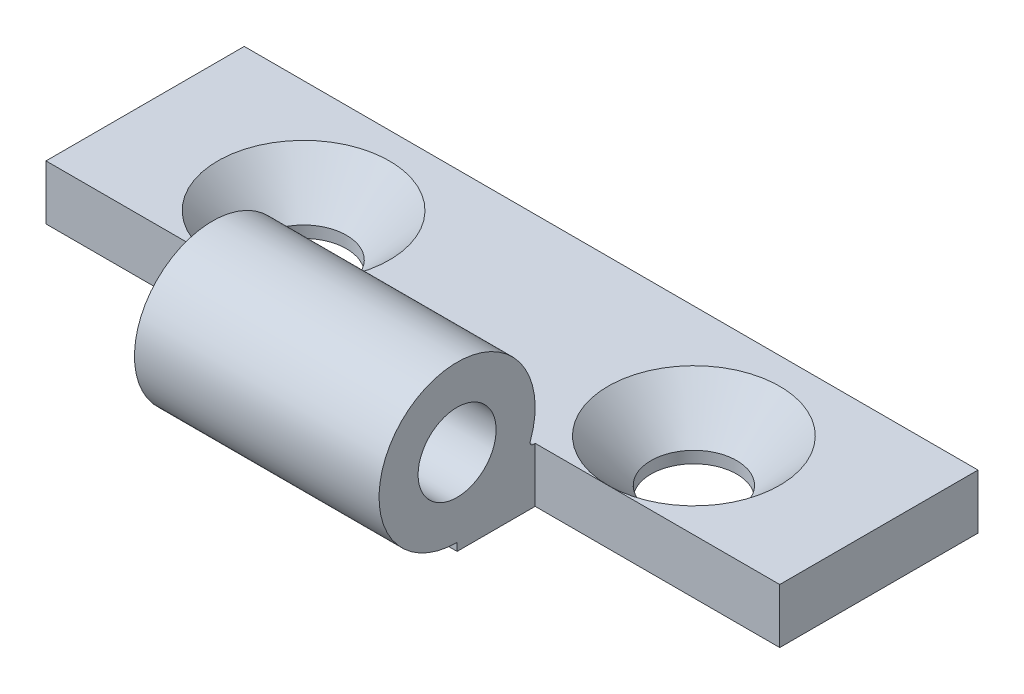
SolidWorks part; units mm, degrees
note: '?' marks a value the reader was unsure of.
ref_plane "Front Plane" through (0, 0, 0) normal (0, 0, 1) x (1, 0, 0)
ref_plane "Top Plane" through (0, 0, 0) normal (0, 1, 0) x (1, 0, 0)
ref_plane "Right Plane" through (0, 0, 0) normal (1, 0, 0) x (0, 0, -1)
ref_axis "Axis_X" through (-13.35, 0, 0) along (1, 0, 0)?
ref_axis "Axis_Y" through (0, 11.025, 0) along (0, -1, 0)?
ref_axis "Axis_Z" through (0, 0, -8.335) along (0, 0, 1)?
ref_plane "K" through (-11, 0, 0) normal (1, 0, 0) x (0, 0, -1)
ref_plane "L" through (36, 0, 0) normal (1, 0, 0) x (0, 0, -1)
sketch "Sketch1" plane through (0, 0, 0) normal (1, 0, 0) x (0, 0, -1)
  line L9 (-10.5, 0.5) -> (-10.5, 0)
  line L10 (7.2, 0) -> (7.2, 3.5)
  line L11 (7.2, 3.5) -> (-5.6215, 3.5)
  line L12 (7.2, 0) -> (-10.5, 0)
  circle A0 centre (-10.5, 5.5) radius 2.5
  arc A3 (-5.8091, 3.7692) -> (-10.5, 0.5) centre (-10.5, 5.5) ccw
  arc A4 (-5.8091, 3.7692) -> (-5.6215, 3.5) centre (-5.6215, 3.7) ccw
  dimension "R" = 5
  dimension "FIX_1" = 5
  dimension "FIX_2" = 0.2
  dimension "T" = 3.5
  dimension "MSM_2" = 17.7
  dimension "E" = 5.5
  dimension "J" = 7.2
extrude "Boss-Extrude1" add sketch "Sketch1" along normal up to surface (36 mm away) and the other way up to surface (11 mm away) up to plane "L" other way up to plane "K"
hole_wizard "CSK1" positions "Sketch3" profile "Sketch2" countersink size "M5" standard "JIS" end condition through all
sketch "Sketch3" plane through (0, 3.5, 0) normal (0, 1, 0) x (1, 0, 0)
  point P0 (0, 0)
  point P3 (25, 0)
  dimension "P" = 25
sketch "Sketch2" plane through (0, 3.5, 0) normal (1, 0, 0) x (0, 0, 1)
  line L0 (0, 0) -> (0, 3.5)
  line L1 (0, 3.5) -> (2.75, 3.5)
  line L2 (2.75, 3.5) -> (2.75, 2.75)
  line L3 (2.75, 2.75) -> (5.5, 0)
  line L5 (5.5, 0) -> (0, 0)
  line L6 (-2.75, 2.75) -> (-5.5, 0) construction
  line L11 (0, -6.35) -> (0, 107.95) construction
  dimension "N_2" = 5.5
  dimension "Thru Hole Depth" = 3.5
  dimension "N_1" = 11
  dimension "Near C'Sink Angle" = 90
sketch "Sketch4" plane through (0, 0, 0) normal (0, 1, 0) x (1, 0, 0)
  line L0 (-11, -5.775) -> (-11, 5.775) construction
  line L1 (-11, -5.5) -> (4.6667, -5.5)
  line L2 (-11, -5.5) -> (-11, -15.5)
  line L3 (-11, -15.5) -> (4.6667, -15.5)
  line L4 (4.6667, -5.5) -> (4.6667, -15.5)
  line L6 (20.3333, -5.5) -> (36, -5.5)
  line L7 (20.3333, -5.5) -> (20.3333, -15.5)
  line L8 (20.3333, -15.5) -> (36, -15.5)
  line L9 (36, -5.5) -> (36, -15.5)
  dimension "KSS_5" = 10
  dimension "KSS_7" = 15.6667
  dimension "KSS_6" = 5
  dimension "KSS_8" = 15.6667
  dimension "KSS_9" = 15.6667
extrude "Cut-Extrude1" cut sketch "Sketch4" along normal through all
hole_wizard "CSK2" [suppressed] positions "Sketch9" profile "Sketch8" countersink size "M5" standard "JIS"
sketch "Sketch9" plane through (0, 3.5, 0) normal (0, 1, 0) x (1, 0, 0)
  line L0 (25, -5.5) -> (25, 7.2) construction
  line L1 (36, -5.5) -> (20, -5.5) construction
  line L2 (36, 7.2) -> (-11, 7.2) construction
  point P0 (0, 0)
  point P2 (25, 0)
  point P4 (50, 0)
  dimension "P" = 25
sketch "Sketch8" plane through (0, 3.5, 0) normal (1, 0, 0) x (0, 0, 1)
  line L0 (0, 0) -> (0, 5.1524)
  line L1 (0, 5.1524) -> (2.75, 3.5)
  line L2 (2.75, 3.5) -> (2.75, 2.75)
  line L3 (2.75, 2.75) -> (5.5, 0)
  line L5 (5.5, 0) -> (0, 0)
  line L6 (-2.75, 2.75) -> (-5.5, 0) construction
  line L10 (0, 5.1524) -> (-2.75, 3.5) construction
  line L11 (0, -6.35) -> (0, 107.95) construction
  dimension "N_2" = 5.5
  dimension "Hole Depth" = 3.5
  dimension "N_1" = 11
  dimension "Near C'Sink Angle" = 90
  dimension "Drill Angle" = 118
equation "\"Factor\"= 1.082532"
equation "\"KSS_5\"= if ( \"MSM_2@Sketch1\" = 17.7 , 10 , 11 )"
equation "\"KSS_6\"= if ( \"MSM_2@Sketch1\" = 17.7 , 5 , 5.5 )"
equation "\"KSS_7@Sketch4\"= \"L@L\" / 3"
equation "\"KSS_8@Sketch4\"= \"KSS_7@Sketch4\""
equation "\"KSS_9@Sketch4\"= \"KSS_7@Sketch4\""
